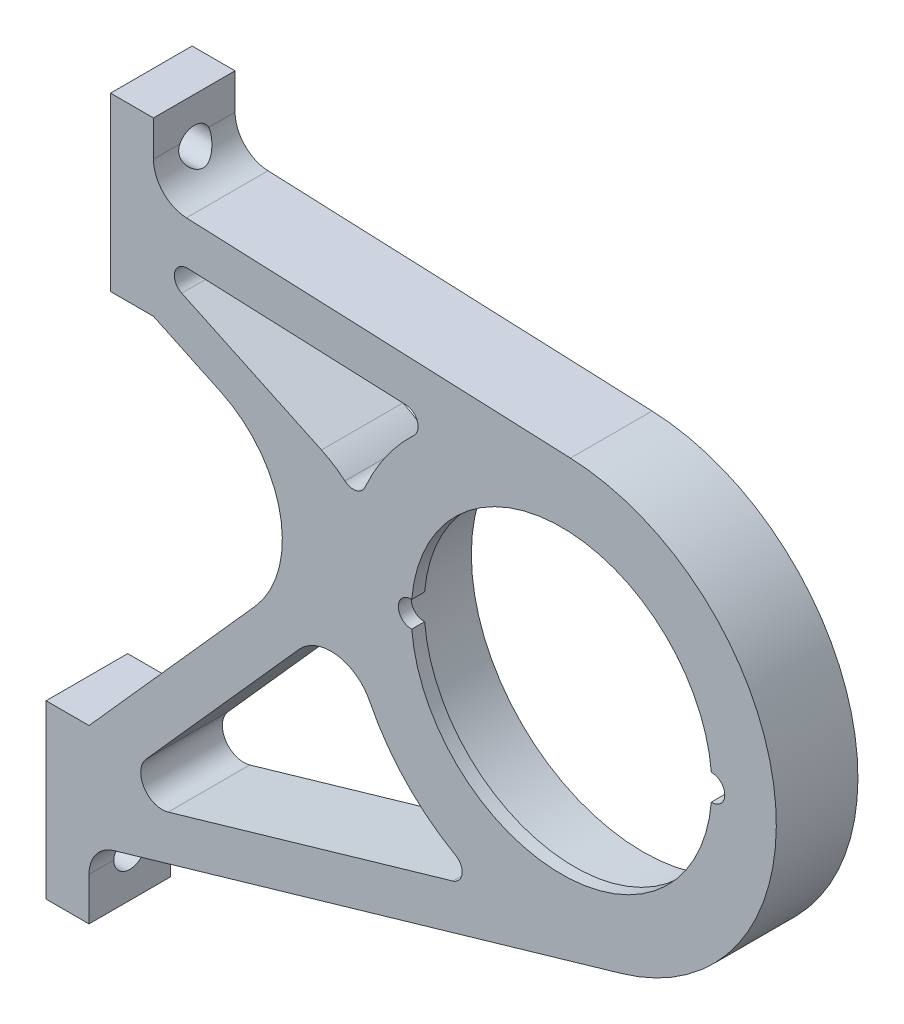
SolidWorks part; units mm, degrees
material "6061 Alloy"
ref_plane "Front Plane" through (0, 0, 0) normal (0, 0, 1) x (1, 0, 0)
ref_plane "Top Plane" through (0, 0, 0) normal (0, 1, 0) x (1, 0, 0)
ref_plane "Right Plane" through (0, 0, 0) normal (1, 0, 0) x (0, 0, -1)
sketch "Sketch1" plane through (0, 0, 0) normal (0, 0, 1) x (1, 0, 0)
  line L0 (-133.35, 88.9) -> (-133.35, 38.1)
  line L1 (-133.35, 38.1) -> (-120.65, 38.1)
  line L2 (-133.35, 88.9) -> (-120.65, 88.9)
  line L3 (-120.65, 88.9) -> (-120.65, 68.58)
  line L4 (-120.65, 68.58) -> (2.6424, 63.445)
  line L5 (-152.4, -76.2) -> (-139.7, -76.2)
  line L6 (-152.4, -76.2) -> (-152.4, -127)
  line L7 (-152.4, -127) -> (-139.7, -127)
  line L8 (-139.7, -127) -> (-139.7, -106.68)
  line L9 (-139.7, -106.68) -> (17.7044, -60.982)
  line L10 (-120.65, 38.1) -> (-100.7551, 28.7158)
  line L11 (-139.7, -76.2) -> (-90.6011, -21.1288)
  line L12 (-46.0374, 52.7615) -> (-110.4951, 55.4461)
  line L13 (-112.2791, 48.1935) -> (-70.9856, 28.7158)
  line L14 (-77.621, -25.6539) -> (-122.808, -76.3375)
  line L15 (-116.2978, -86.6614) -> (-32.1185, -62.2223)
  arc A0 (-56.7845, -28.4212) -> (-31.3026, -55.2485) centre (0, 0) ccw
  circle A1 centre (0, 0) radius 50.8
  arc A2 (-90.6011, -21.1288) -> (-100.7551, 28.7158) centre (-114.3, 0) ccw
  arc A3 (-64.0429, 24.2554) -> (-70.9856, 28.7158) centre (-84.5305, 0) ccw
  arc A4 (-110.4951, 55.4461) -> (-112.2791, 48.1935) centre (-110.6537, 51.6394) ccw
  arc A6 (-122.808, -76.3375) -> (-116.2978, -86.6614) centre (-118.0683, -80.5632) ccw
  arc A7 (17.7044, -60.982) -> (2.6424, 63.445) centre (0, 0) ccw
  arc A8 (-43.5811, 46.1837) -> (-58.0985, 25.6283) centre (0, 0) ccw
  arc A9 (-46.0374, 52.7615) -> (-43.5811, 46.1837) centre (-46.196, 48.9548) cw
  arc A10 (-64.0429, 24.2554) -> (-58.0985, 25.6283) centre (-61.5844, 27.166) ccw
  arc A11 (-32.1185, -62.2223) -> (-31.3026, -55.2485) centre (-33.1808, -58.5634) ccw
  arc A12 (-77.621, -25.6539) -> (-56.7845, -28.4212) centre (-68.1415, -34.1055) cw
  point P44 (-35.9531, 52.3414)
  dimension "D1" = 12.7
  dimension "D2" = 101.6
  dimension "D13" = 63.5
  dimension "D14" = 31.75
  dimension "D17" = 3.81
  dimension "D18" = 31.75
  dimension "D21" = 6.35
  dimension "D22" = 3.81
  dimension "D23" = 3.81
  dimension "D24" = 12.7
  dimension "D3" = 50.8
  dimension "D4" = 12.7
  dimension "D5" = 20.32
  dimension "D6" = 133.35
  dimension "D7" = 152.4
  dimension "D8" = 12.7
  dimension "D9" = 50.8
  dimension "D10" = 20.32
  dimension "D11" = 88.9
  dimension "D12" = 127
  dimension "D15" = 12.7
  dimension "D16" = 12.7
  dimension "D19" = 12.7
  dimension "D20" = 12.7
extrude "Boss-Extrude1" add sketch "Sketch1" along normal blind 24.13
fillet "Fillet1" radius 10.16 2 edges at (-139.7, -106.68, 12.065) (-120.65, 68.58, 12.065)
sketch "Sketch2" plane through (-152.4, 0, 0) normal (-1, 0, 0) x (0, 0, 1)
  line L0 (24.13, 88.9) -> (0, 88.9) construction
  line L1 (24.13, -127) -> (0, -127) construction
  circle A0 centre (12.065, -114.3) radius 4.7625
  circle A1 centre (12.065, 76.2) radius 4.7625
  point P6 (12.065, 88.9)
  dimension "D1" = 9.525
  dimension "D2" = 12.7
  dimension "D3" = 12.7
extrude "Cut-Extrude1" cut sketch "Sketch2" against normal through all
sketch "Sketch3" plane through (0, 0, 24.13) normal (0, 0, 1) x (1, 0, 0)
  arc A0 (-44.2867, -3.8065) -> (44.2867, -3.8065) centre (0, 0) ccw
  arc A1 (-44.2867, 3.8065) -> (-44.2867, -3.8065) centre (-44.45, 0) ccw
  circle A2 centre (0, 0) radius 50.8 construction
  circle A3 centre (0, 0) radius 50.8
  arc A4 (44.2867, -3.8065) -> (44.2867, 3.8065) centre (44.45, 0) ccw
  arc A5 (44.2867, 3.8065) -> (-44.2867, 3.8065) centre (0, 0) ccw
  circle M24 centre (0, 0) radius 50.8
  dimension "D1" = 88.9
  dimension "D2" = 2.54
  dimension "D3" = 2.54
extrude "Boss-Extrude2" add sketch "Sketch3" against normal blind 3.81 contours A5 A4 A1 M24 | A4 A0 A1 A3 region at (-49.3632, 0, 24.13)
